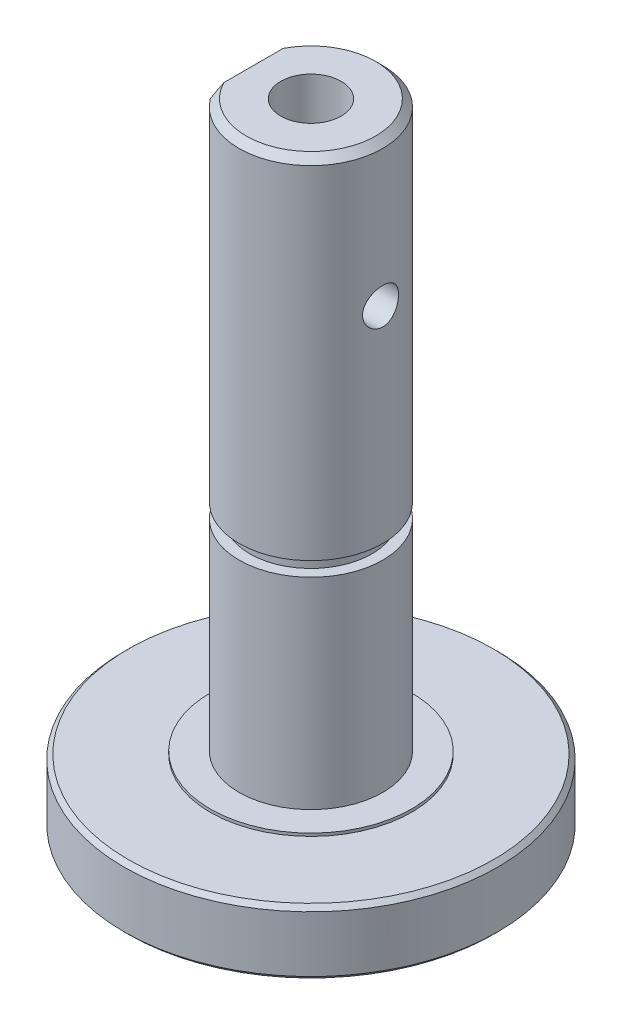
SolidWorks part; units mm, degrees
material "AISI 1045 钢，冷拔"
ref_plane "前视基准面" through (0, 0, 0) normal (0, 0, 1) x (1, 0, 0)
ref_plane "上视基准面" through (0, 0, 0) normal (0, 1, 0) x (1, 0, 0)
ref_plane "右视基准面" through (0, 0, 0) normal (1, 0, 0) x (0, 0, -1)
ref_plane "基准面1" through (0, 0, 0) normal (0, 0, -1) x (-1, 0, 0)
sketch "草图1" plane through (0, 0, 0) normal (0, 0, -1) x (-1, 0, 0)
  line L0 (-13, 0) -> (0, 0)
  line L1 (0, 0) -> (0, 44)
  line L2 (0, 44) -> (-5, 44)
  line L3 (-5, 44) -> (-5, 19.7)
  line L4 (-5, 19.7) -> (-4.25, 19.7)
  line L5 (-4.25, 19.7) -> (-4.25, 18.7)
  line L6 (-4.25, 18.7) -> (-5, 18.7)
  line L7 (-5, 18.7) -> (-5, 4.7)
  line L8 (-5, 4.7) -> (-7, 4.7)
  line L9 (-7, 4.7) -> (-7, 4.5)
  line L10 (-7, 4.5) -> (-13, 4.5)
  line L11 (-13, 4.5) -> (-13, 0)
  line L12 (0, 0) -> (0, 44) construction
revolve "旋转1" add sketch "草图1" angle 360 about L12 reverse direction yes
sketch "草图2" plane through (0, 44, 0) normal (0, 1, 0) x (-1, 0, 0)
  line L0 (4, 3) -> (4, -3)
  arc A0 (4, -3) -> (4, 3) centre (0, 0) ccw
extrude "切除-拉伸1" cut sketch "草图2" against normal blind 20
hole_wizard "Ø4.2 (4.2) 直径孔1" positions "草图4" profile "草图3" hole size "Ø4.2" standard "ANSI Metric"
sketch "草图4" plane through (0, 44, 0) normal (0, 1, 0) x (1, 0, 0)
  point P0 (0, 0)
sketch "草图3" plane through (0, 44, 0) normal (1, 0, 0) x (0, 0, 1)
  line L0 (0, 0) -> (0, 15.2618)
  line L1 (0, 15.2618) -> (2.1, 14)
  line L2 (2.1, 14) -> (2.1, 0)
  line L5 (2.1, 0) -> (0, 0)
  line L10 (0, 15.2618) -> (-2.1, 14) construction
  line L11 (0, -6.35) -> (0, 107.95) construction
  dimension "孔直径" = 4.2
  dimension "孔深度" = 14
  dimension "导头角度" = 118
hole_wizard "Ø2.5 (2.5) 直径孔1" positions "草图6" profile "草图5" hole size "Ø2.5" standard "ANSI Metric"
sketch "草图6" plane through (-4, 0, 0) normal (-1, 0, 0) x (0, 0, 1)
  point P0 (0, 34)
sketch "草图5" plane through (-4, 34, 0) normal (0, 1, 0) x (0, 0, 1)
  line L0 (0, 0) -> (0, 12.3125)
  line L1 (0, 12.3125) -> (1.25, 12.3125)
  line L2 (1.25, 12.3125) -> (1.25, 0)
  line L5 (1.25, 0) -> (0, 0)
  line L10 (0, 12.3125) -> (-1.25, 12.3125) construction
  line L11 (0, -6.35) -> (0, 107.95) construction
  dimension "孔直径" = 2.5
  dimension "孔深度" = 12.3125
  dimension "导头角度" = 180
chamfer "倒角1" distance 0.3 angle 45 2 edges at (0, 4.5, 13) (0, 0, 13)
chamfer "倒角2" distance 0.5 angle 45 1 edges at (5, 44, 0)
